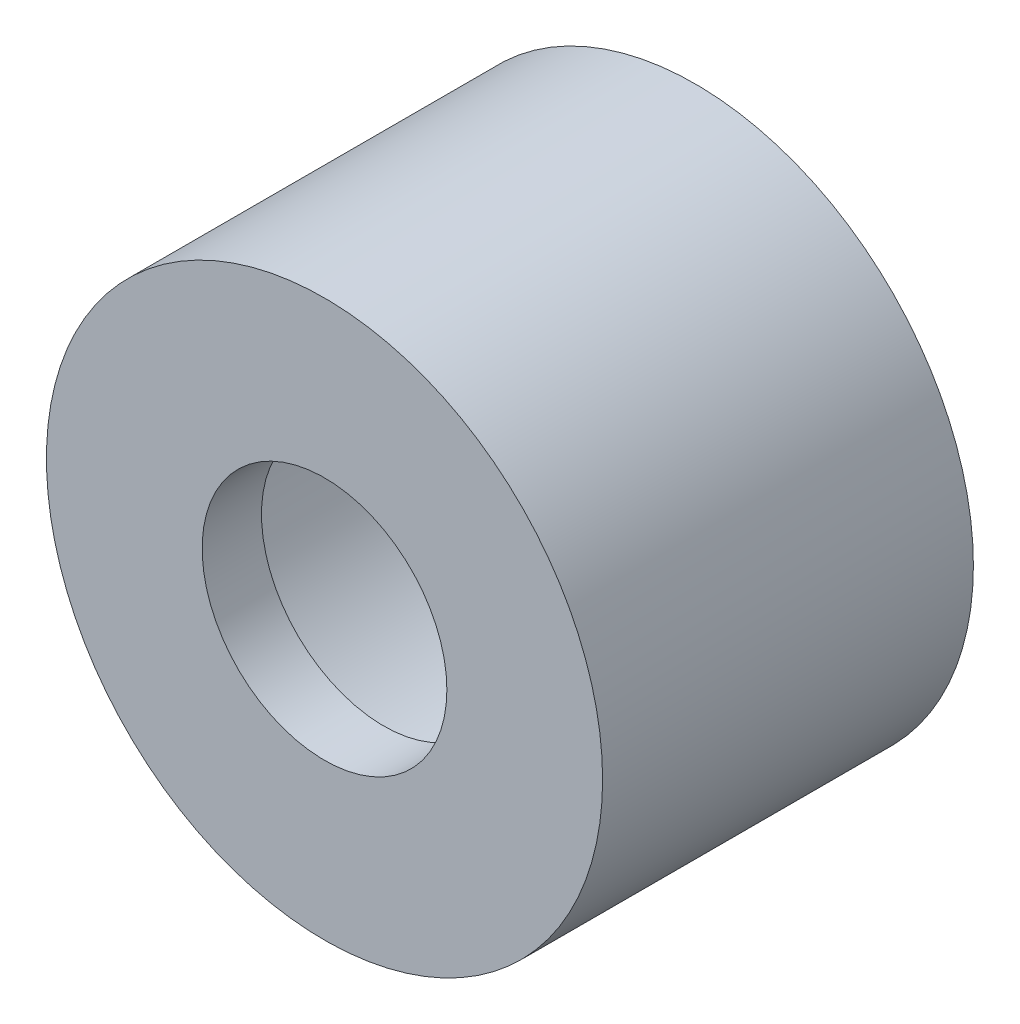
SolidWorks part; units mm, degrees
note: '?' marks a value the reader was unsure of.
ref_plane "Płaszczyzna przednia" through (0, 0, 0) normal (0, 0, 1) x (1, 0, 0)
ref_plane "Płaszczyzna górna" through (0, 0, 0) normal (0, 1, 0) x (1, 0, 0)
ref_plane "Płaszczyzna prawa" through (0, 0, 0) normal (1, 0, 0) x (0, 0, -1)
sketch "Szkic1" plane through (0, 0, 0) normal (1, 0, 0) x (0, 0, -1)
  line L0 (-10, 0) -> (-10, 7.5)
  line L1 (-10, 7.5) -> (0, 7.5)
  line L2 (0, 7.5) -> (0, 0)
  line L3 (0, 0) -> (-10, 0)
  line L4 (0, 0) -> (-10, 0) construction
sketch "Szkic2" plane through (0, 0, 0) normal (1, 0, 0) x (0, 0, -1)
  line L0 (-10, 0) -> (-10, 3.3)
  line L1 (-10, 3.3) -> (-8.4, 3.3)
  line L2 (-8.4, 3.3) -> (-8.4, 5.5)
  line L3 (-8.4, 5.5) -> (0, 5.5)
  line L4 (0, 5.5) -> (0, 0)
  line L5 (0, 0) -> (-10, 0)
  line L6 (0, 0) -> (-10, 0) construction
revolve "Obrót1" add sketch "Szkic1" angle 360 about L4
revolve "Wycięcie-obrót1" cut sketch "Szkic2" angle 360 about L6
ref_plane "Płaszczyzna1" through (0, 0, 10) normal (0, 0, 1) x (1, 0, 0)
ref_plane "IP2 XY" through (0, 0, 10) normal (0, 0, 1) x (1, 0, 0)
ref_plane "IP2 XZ" through (0, 0, 0) normal (0, -1, 0) x (-1, 0, 0)
ref_plane "IP2 YZ" through (0, 0, 0) normal (1, 0, 0) x (0, 0, -1)
ref_axis "IP2 X" through (-80.9, 0, 10) along (1, 0, 0)?
ref_axis "IP2 Y" through (0, -50, 10) along (0, 1, 0)?
ref_axis "IP2 Z" through (0, 0, 80.9) along (0, 0, -1)?
sketch3d "IP2"
  point P0 (0, 0, 10)
ref_plane "IP1 XY" through (0, 0, 0) normal (0, 0, 1) x (1, 0, 0)
ref_plane "IP1 XZ" through (0, 0, 0) normal (0, -1, 0) x (-1, 0, 0)
ref_plane "IP1 YZ" through (0, 0, 0) normal (1, 0, 0) x (0, 0, -1)
ref_axis "IP1 X" through (-80.9, 0, 0) along (1, 0, 0)?
ref_axis "IP1 Y" through (0, -50, 0) along (0, 1, 0)?
ref_axis "IP1 Z" through (0, 0, 80.9) along (0, 0, -1)?
sketch3d "IP1"
  point P0 (0, 0, 0)
sketch "Szkic3" plane through (0, 0, 0) normal (1, 0, 0) x (0, 0, -1)
  circle A0 centre (0, 0) radius 5.625
extrude "Dodanie-wyciągnięcie1" add sketch "Szkic3" along normal blind 3.75 separate body
other "Usuń ścianę1" face at (3.75, 0, -5.625)
